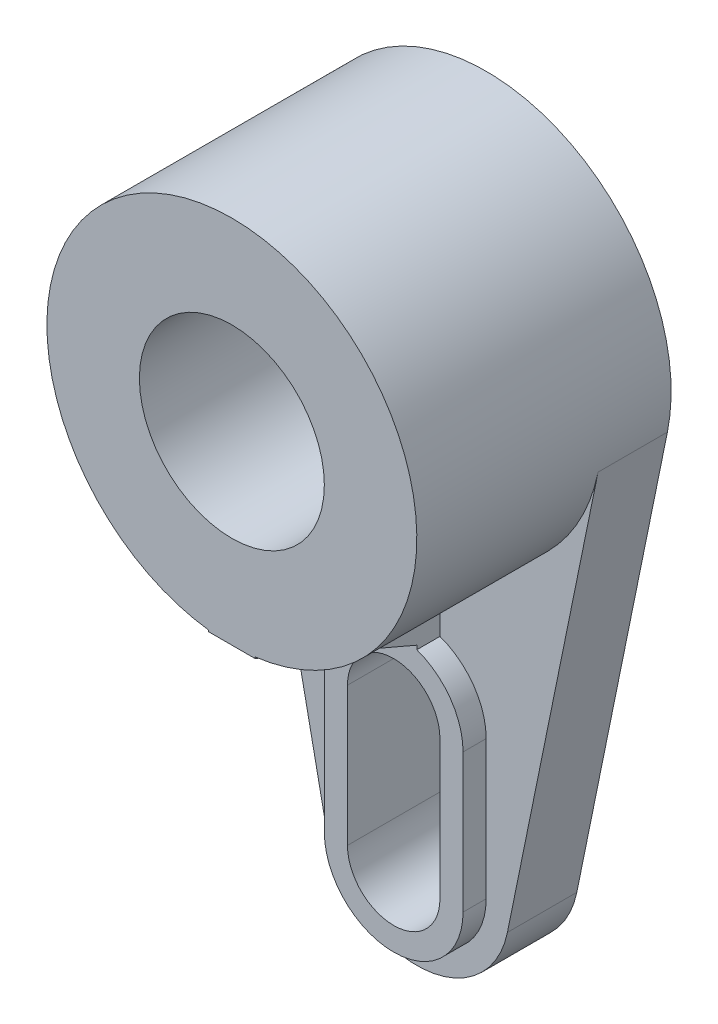
SolidWorks part; units mm, degrees
ref_plane "Front Plane" through (0, 0, 0) normal (1, 0, 0) x (0, 1, 0)
ref_plane "Top Plane" through (0, 0, 0) normal (0, 0, 1) x (0, 1, 0)
ref_plane "Right Plane" through (0, 0, 0) normal (0, 1, 0) x (-1, 0, 0)
sketch "Sketch1" plane through (0, 0, 0) normal (0, 0, 1) x (0, 1, 0)
  line L0 (0, 0) -> (0, 49847.8227) construction
  line L1 (0, 0) -> (49847.8227, 0) construction
  line L2 (-100, 0) -> (-70, 0) construction
  line L3 (-100, 10) -> (-70, 10)
  line L4 (-100, -10) -> (-70, -10)
  line L5 (-104, 19.5959) -> (-8, 39.1918)
  line L6 (-104, -19.5959) -> (-8, -39.1918)
  line L7 (-100, 15) -> (-70, 15)
  line L8 (-100, -15) -> (-70, -15)
  circle A0 centre (0, 0) radius 20
  circle A1 centre (0, 0) radius 40
  arc A2 (-104, 19.5959) -> (-104, -19.5959) centre (-100, 0) ccw
  arc A3 (-100, 10) -> (-100, -10) centre (-100, 0) ccw
  arc A4 (-70, -10) -> (-70, 10) centre (-70, 0) ccw
  arc A5 (-70, -15) -> (-70, 15) centre (-70, 0) ccw
  arc A6 (-100, 15) -> (-100, -15) centre (-100, 0) ccw
  point P11 (-85, 0)
  dimension "D1" = 40
  dimension "D2" = 80
  dimension "D3" = 40
  dimension "D5" = 10
  dimension "D4" = 100
  dimension "D6" = 30
  dimension "D7" = 5
extrude "Boss-Extrude1" add sketch "Sketch1" along normal blind 15 contours L5 A2 L6 A1 A6 L7 A5 L8 region at (-28.0545, -55.7266, 0)
extrude "Boss-Extrude2" add sketch "Sketch1<3>" along normal blind 20 contours L7 A6 L8 A5 A4 L4 A3 L3 region at (-14.3292, -85, 0)
sketch "Sketch1<3>" plane through (0, 0, 0) normal (0, 0, 1) x (0, 1, 0) same geometry as "Sketch1"
extrude "Boss-Extrude3" add sketch "Sketch1<4>" along normal blind 55 contours A1 A0 region at (-30.1075, 24.5827, 0)
sketch "Sketch1<4>" plane through (0, 0, 0) normal (0, 0, 1) x (0, 1, 0) same geometry as "Sketch1"
sketch "Sketch2" plane through (0, 0, 0) normal (1, 0, 0) x (0, 1, 0)
  line L0 (-55, 20) -> (-40, 55)
  line L4 (-40, 55) -> (-39, 55)
  line L5 (40, 55) -> (-40, 55) construction
  line L6 (-39, 55) -> (-39, 15)
  line L7 (-104, 15) -> (-8, 15) construction
  line L8 (-39, 15) -> (-56, 15)
  line L9 (-56, 15) -> (-56, 20)
  line L10 (-55, 20) -> (-70, 20) construction
  line L11 (-56, 20) -> (-55, 20)
  dimension "D1" = 1
  dimension "D2" = 1
extrude "Boss-Extrude6" add sketch "Sketch2" along normal mid plane 10
